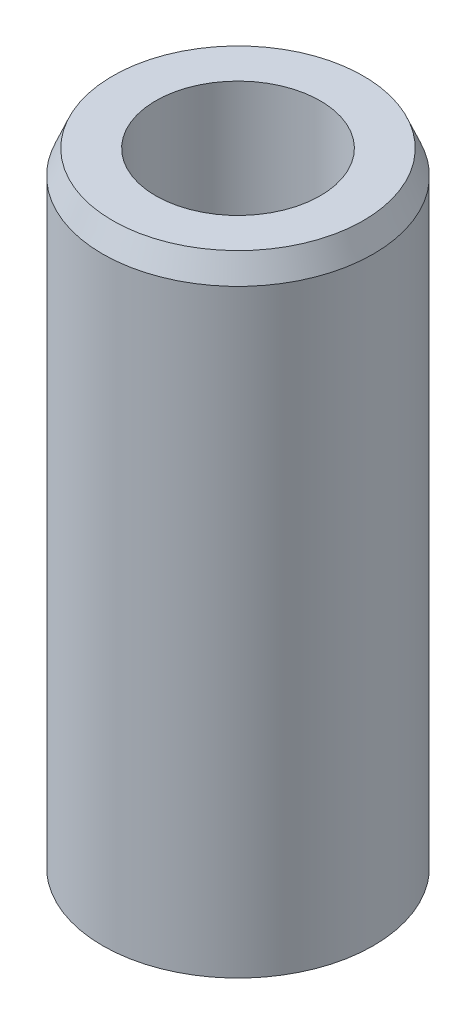
SolidWorks part; units mm, degrees
ref_plane "Front Plane" through (0, 0, 0) normal (0, 0, 1) x (1, 0, 0)
ref_plane "Top Plane" through (0, 0, 0) normal (0, 1, 0) x (1, 0, 0)
ref_plane "Right Plane" through (0, 0, 0) normal (1, 0, 0) x (0, 0, -1)
sketch "Sketch1" plane through (0, 0, 0) normal (0, 1, 0) x (1, 0, 0)
  circle A0 centre (0, 0) radius 17.5
  dimension "SHAFT_OD" = 35
extrude "Boss-Extrude1" add sketch "Sketch1" along normal blind 81.8251
sketch "Sketch2" plane through (0, 0, 0) normal (0, 1, 0) x (1, 0, 0)
  circle A0 centre (0, 0) radius 10.6419
  dimension "BORE_D" = 21.2839
extrude "Cut-Extrude1" cut sketch "Sketch2" along normal through all
chamfer "Chamfer1" distance 3.0899 angle 22.766 2 edges at (0, 81.8251, 17.5) (0, 0, 17.5) first distance on face at (0, 81.8251, 17.5) first distance on face at (0, 0, 10.6419)
